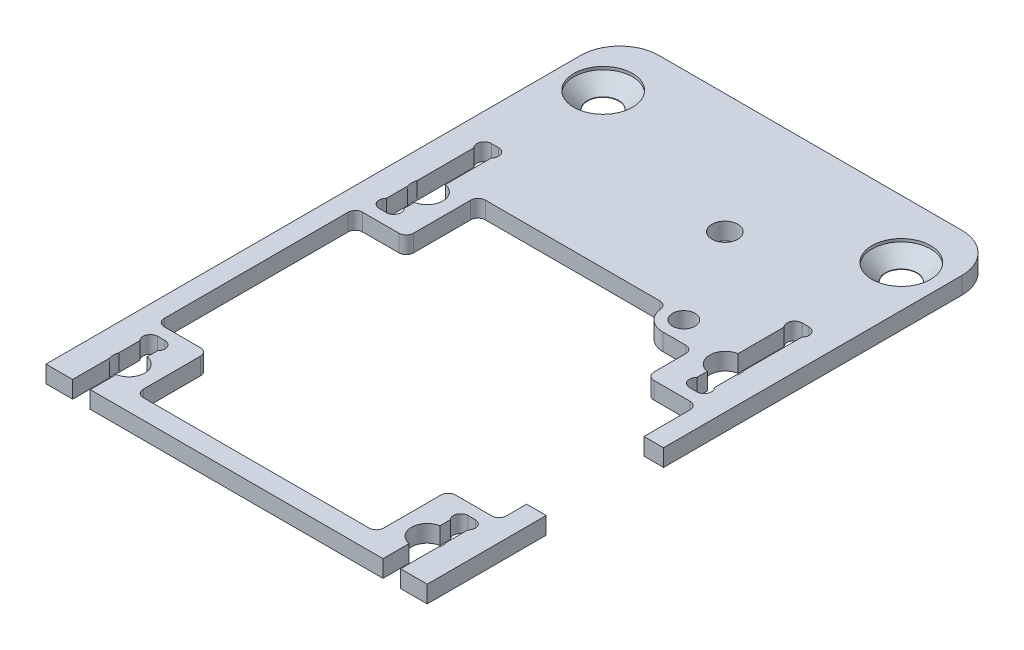
SolidWorks part; units mm, degrees
ref_plane "Front Plane" through (0, 0, 0) normal (0, 0, 1) x (1, 0, 0)
ref_plane "Top Plane" through (0, 0, 0) normal (0, 1, 0) x (1, 0, 0)
ref_plane "Right Plane" through (0, 0, 0) normal (1, 0, 0) x (0, 0, -1)
sketch "Sketch1" plane through (0, 0, 0) normal (0, 1, 0) x (1, 0, 0)
  line L0 (-15.5, 39.2) -> (15.5, 39.2)
  line L1 (-18.2, 15) -> (-18.2, -15) construction
  line L2 (17.5, -17.4996) -> (-17.5, -17.4996)
  line L3 (17.5, -17.4996) -> (17.5, 17.4996)
  line L4 (17.5, 17.4996) -> (-17.5, 17.4996)
  line L5 (-17.5, -17.4996) -> (-17.5, 17.4996)
  line L6 (17.5, -17.4996) -> (-17.5, 17.4996) construction
  line L7 (-19.5, 35.2) -> (-19.5, -19.5)
  line L8 (-19.5, -19.5) -> (19.5, -19.5)
  line L9 (19.5, -19.5) -> (19.5, 35.2)
  line L10 (17.5, 17.4996) -> (-17.5, -17.4996) construction
  line L11 (-15.25, 15.25) -> (-15.25, 17.9996) construction
  line L12 (11.35, 17.05) -> (11.35, 17.4996)
  line L13 (7.05, 17.05) -> (7.05, 17.4996)
  line L14 (15.25, -13.65) -> (15.25, -10.15) construction
  line L15 (17.5, -10.15) -> (12.3, -10.15)
  line L16 (-17.5, -10.15) -> (-12.3, -10.15)
  line L17 (-12.3, -10.15) -> (-12.3, -15.25)
  line L18 (12.3, -10.15) -> (12.3, -15.25)
  line L19 (0, 39.2) -> (0, -19.5) construction
  line L20 (-12.3, -15.25) -> (-12.3, -17.4996)
  line L21 (12.3, -15.25) -> (12.3, -17.4996)
  line L22 (-15.25, 13.65) -> (-15.25, 10.15) construction
  line L23 (-12.3, 17.4996) -> (-17.5, 17.4996)
  line L24 (-12.3, 17.4996) -> (-12.3, 10.15)
  line L25 (-12.3, 10.15) -> (-17.5, 10.15)
  line L26 (-17.5, 17.4996) -> (-17.5, 10.15)
  line L27 (12.3, 17.4996) -> (12.3, 10.15)
  line L28 (12.3, 10.15) -> (17.5, 10.15)
  line L29 (9.2, 14.9) -> (12.3, 14.9)
  arc A0 (19.5, 35.2) -> (15.5, 39.2) centre (15.5, 35.2) ccw construction
  arc A1 (-15.5, 39.2) -> (-19.5, 35.2) centre (-15.5, 35.2) ccw construction
  arc A2 (19.5, 35.2) -> (15.5, 39.2) centre (15.5, 35.2) ccw
  arc A3 (-15.5, 39.2) -> (-19.5, 35.2) centre (-15.5, 35.2) ccw
  circle A4 centre (-15.25, -15.25) radius 1.6 construction
  circle A5 centre (15.25, -15.25) radius 1.6 construction
  circle A6 centre (-15.25, 15.25) radius 1.6 construction
  circle A7 centre (15.25, 15.25) radius 1.6 construction
  circle A8 centre (-15.25, 33.25) radius 1.6 construction
  circle A9 centre (15.25, 33.25) radius 1.6 construction
  circle A10 centre (-15.25, -15.25) radius 1.6
  circle A11 centre (15.25, -15.25) radius 1.6
  circle A12 centre (-15.25, 15.25) radius 1.6
  circle A13 centre (15.25, 15.25) radius 1.6
  circle A14 centre (-15.25, 33.25) radius 1.6
  circle A15 centre (15.25, 33.25) radius 1.6
  arc A16 (-15.2, 18) -> (-18.2, 15) centre (-15.2, 15) ccw construction
  circle A17 centre (-15.25, 15.25) radius 2.95
  circle A18 centre (15.25, 15.25) radius 2.95
  circle A19 centre (-15.25, -15.25) radius 2.95
  circle A20 centre (15.25, -15.25) radius 2.95
  circle A21 centre (3.5, 26.95) radius 1.33 construction
  circle A22 centre (9.2, 17.05) radius 2.15
  circle A23 centre (9.2, 17.05) radius 1.15
  circle A24 centre (9.2, 17.05) radius 0.9 construction
  circle A25 centre (3.5, 26.95) radius 1.33
  point P29 (0, 0)
  dimension "D3" = 2.3
  dimension "D4" = 1
  dimension "D1" = 2
  dimension "D2" = 0.5
  dimension "D6" = 3.5
extrude "Base shape" add sketch "Sketch1" along normal blind 1.75 contours L0 A3 L7 L8 L9 A2 A25 A22 L4 A18 L3 A20 L2 A19 L5 A17 A15 A14 | L23 A17 | A17 L4 L5 | L23 A17 L26 A12 | L26 A17 | A17 L24 L4 | A17 L5 L25 L24 | A23 L4 A22 | A22 L12 L4 | A23 L4 A22 | A22 L29 L27 L4 L12 | A18 L4 L27 | L3 A18 L4 A13 | L4 A18 | A18 L3 L4 | L3 A18 | A18 L27 L28 L3 | A20 L3 L15 L18 | L2 A20 L3 A11 | L3 A20 | A20 L2 L3 | L2 A20 | A20 L21 L2 | L5 A19 | A19 L5 L2 | L2 A19 | L2 A19 L5 A10 | A19 L2 L20 | A19 L17 L16 L5 region at (-0.0675, 0, -21.1692) region at (12.6001, 0, 16.959) region at (-12.6001, 0, 16.959) region at (12.6398, 0, 16.4586) region at (15.25, 0, 17.7828) region at (14.7438, 0, 11.5319) region at (-15.25, 0, 17.7828) region at (-15.25, 0, 17.426) region at (-14.7438, 0, 11.5319) region at (17.3893, 0, 17.3888) region at (17.7831, 0, 15.25) region at (-17.3893, 0, 17.3888) region at (-17.7831, 0, 15.25) region at (14.7438, 0, -11.5319) region at (-14.7438, 0, -11.5319) region at (14.2592, 0, -12.5496) region at (17.7831, 0, -15.25) region at (-17.7831, 0, -15.25) region at (-17.4265, 0, -15.25) region at (17.3893, 0, -17.3888) region at (11.5513, 0, -15.9649) region at (12.6001, 0, -16.959) region at (-17.3893, 0, -17.3888) region at (-12.6001, 0, -16.959) region at (15.25, 0, -17.7828) region at (7.7153, 0, -15.5653) region at (-15.25, 0, -17.7828) region at (11.3358, 0, -17.3874) region at (9.2, 0, -18.3154)
fillet "Milling fillets" radius 0.75 13 edges at (17.5, 0.875, 10.15) (-17.5, 0.875, 10.15) (-12.3, 0.875, 10.15) (12.3, 0.875, 10.15) (12.3, 0.875, 17.4996) (-12.3, 0.875, 17.4996) (17.5, 0.875, -10.15) (12.3, 0.875, -10.15) (12.3, 0.875, -14.9) (7.0975, 0.875, -17.4996) (-12.3, 0.875, -17.4996) (-12.3, 0.875, -10.15) (-17.5, 0.875, -10.15)
sketch "Sketch3" plane through (0, 1.75, 0) normal (0, 1, 0) x (1, 0, 0)
  circle A0 centre (-15.25, 33.25) radius 3
  circle A1 centre (15.25, 33.25) radius 3
  dimension "D1" = 6
extrude "Screw head cut" cut sketch "Sketch3" against normal blind 0.3
chamfer "Screw head chamfer" distance 1.4 angle 45 2 edges at (15.25, 1.45, -31.65) (-15.25, 1.45, -31.65)
sketch "Sketch4" plane through (19.5, 0, 0) normal (1, 0, 0) x (0, 0, -1)
  line L0 (4.175, 1) -> (4.175, 0.2) construction
  line L1 (4.175, 1) -> (4.175, 0.2)
  line L2 (-6.825, 1) -> (-6.825, 0.2) construction
  line L3 (-6.825, 1) -> (-6.825, 0.2)
  line L4 (-6.825, 1) -> (4.175, 0.2) construction
  line L5 (-19.5, 0) -> (35.2, 0) construction
  line L6 (4.675, 0) -> (-7.325, 0)
  line L7 (4.675, 0) -> (4.675, 1.2)
  line L8 (4.675, 1.2) -> (-7.325, 1.2)
  line L9 (-7.325, 0) -> (-7.325, 1.2)
  line L10 (4.675, 0) -> (-7.325, 1.2) construction
  line L11 (4.675, 1.2) -> (-7.325, 0) construction
  line L12 (-19.5, 1.75) -> (35.2, 1.75) construction
  line L13 (4.675, 1.2) -> (-7.325, 1.2)
  line L14 (4.675, 1.2) -> (4.675, 1.75)
  line L15 (4.675, 1.75) -> (-7.325, 1.75)
  line L16 (-7.325, 1.2) -> (-7.325, 1.75)
  point P4 (-1.325, 0.6)
  line M6 (35.2, 1.75) -> (-19.5, 1.75)
  dimension "D1" = 0.5
extrude "SD card cut" cut sketch "Sketch4" against normal up to next contours L9 L7 L8 | L16 L8 L14 M6 region at (19.5, 0.6, 1.325) region at (19.5, 1.475, 1.325)
sketch "Sketch5" plane through (0, 1.75, 0) normal (0, 1, 0) x (1, 0, 0)
  line L0 (-15, 0) -> (15, 0) construction
  line L1 (-15, 0) -> (-16.75, 0) construction
  line L2 (-15.875, -19.5) -> (-15.875, 39.2) construction
  line L3 (-19.5, -19.5) -> (19.5, -19.5) construction
  line L4 (-15.5, 39.2) -> (15.5, 39.2) construction
  line L5 (-15.25, -13.65) -> (-15.25, -11.55) construction
  line L6 (-14.975, -11.55) -> (-16.775, -11.55)
  line L7 (-14.975, -11.55) -> (-14.975, -14.7659)
  line L8 (-14.975, -14.7659) -> (-16.775, -14.7659)
  line L9 (-16.775, -11.55) -> (-16.775, -14.7659)
  line L10 (-14.975, -11.55) -> (-16.775, -14.7659) construction
  line L11 (-14.975, -14.7659) -> (-16.775, -11.55) construction
  line L12 (-16.775, -11.55) -> (-14.975, -13.35) construction
  line L13 (-16.2447, -11.3303) -> (-15.5053, -11.3303)
  line L14 (0, -19.5) -> (0, 39.2) construction
  line L15 (-14.975, -19.5) -> (-16.775, -19.5)
  line L16 (-14.975, -19.5) -> (-14.975, -15.7341)
  line L17 (-14.975, -15.7341) -> (-16.775, -15.7341)
  line L18 (-16.775, -19.5) -> (-16.775, -15.7341)
  line L19 (-14.975, -19.5) -> (-16.775, -15.7341) construction
  line L20 (-14.975, -15.7341) -> (-16.775, -19.5) construction
  line L21 (14.975, -19.5) -> (16.775, -19.5)
  line L22 (14.975, -19.5) -> (14.975, -15.7341)
  line L23 (14.975, -15.7341) -> (16.775, -15.7341)
  line L24 (16.775, -19.5) -> (16.775, -15.7341)
  line L25 (16.775, -11.55) -> (16.775, -14.7659)
  line L26 (14.975, -14.7659) -> (16.775, -14.7659)
  line L27 (14.975, -11.55) -> (14.975, -14.7659)
  line L28 (16.2447, -11.3303) -> (15.5053, -11.3303)
  line L29 (16.775, 11.55) -> (16.775, 14.7659)
  line L30 (16.2447, 11.3303) -> (15.5053, 11.3303)
  line L31 (14.975, 11.55) -> (14.975, 14.7659)
  line L32 (14.975, 14.7659) -> (16.775, 14.7659)
  line L33 (-16.775, 11.55) -> (-16.775, 14.7659)
  line L34 (-16.2447, 11.3303) -> (-15.5053, 11.3303)
  line L35 (-14.975, 11.55) -> (-14.975, 14.7659)
  line L36 (-14.975, 14.7659) -> (-16.775, 14.7659)
  line L37 (-15.25, 16.85) -> (-15.25, 22.6) construction
  line L38 (-16.775, 22.6) -> (-14.975, 22.6)
  line L39 (-16.775, 22.6) -> (-16.775, 15.7341)
  line L40 (-16.775, 15.7341) -> (-14.975, 15.7341)
  line L41 (-14.975, 22.6) -> (-14.975, 15.7341)
  line L42 (-16.775, 22.6) -> (-14.975, 15.7341) construction
  line L43 (-16.775, 15.7341) -> (-14.975, 22.6) construction
  line L44 (-16.775, 22.6) -> (-14.975, 20.8) construction
  line L45 (-16.2447, 22.8197) -> (-15.5053, 22.8197)
  line L46 (16.2447, 22.8197) -> (15.5053, 22.8197)
  line L47 (14.975, 22.6) -> (14.975, 15.7341)
  line L48 (16.775, 15.7341) -> (14.975, 15.7341)
  line L49 (16.775, 22.6) -> (16.775, 15.7341)
  circle A0 centre (-15.25, -15.25) radius 1.6 construction
  circle A1 centre (-16.2447, -12.0803) radius 0.75
  circle A2 centre (-15.5053, -12.0803) radius 0.75
  circle A3 centre (15.5053, -12.0803) radius 0.75
  circle A4 centre (16.2447, -12.0803) radius 0.75
  circle A5 centre (16.2447, 12.0803) radius 0.75
  circle A6 centre (15.5053, 12.0803) radius 0.75
  circle A7 centre (-16.2447, 12.0803) radius 0.75
  circle A8 centre (-15.5053, 12.0803) radius 0.75
  circle A9 centre (-15.25, 15.25) radius 1.6 construction
  circle A10 centre (-16.2447, 22.0697) radius 0.75
  circle A11 centre (-15.5053, 22.0697) radius 0.75
  circle A12 centre (16.2447, 22.0697) radius 0.75
  circle A13 centre (15.5053, 22.0697) radius 0.75
  point P3 (0, 0)
  point P11 (-15.875, 0)
  point P12 (-15.875, -13.1579)
  point P29 (-15.875, -17.6171)
  point P70 (-15.875, 19.1671)
  circle M12 centre (-15.25, 15.25) radius 1.6
  circle M13 centre (-15.25, -15.25) radius 1.6
  circle M14 centre (15.25, -15.25) radius 1.6
  circle M15 centre (15.25, 15.25) radius 1.6
  line M52 (-19.5, -19.5) -> (19.5, -19.5)
  dimension "D6" = 1.5
  dimension "D9" = 1.5
  dimension "D1" = 30
  dimension "D2" = 1.75
  dimension "D3" = 1.8
  dimension "D4" = 2.1
  dimension "D5" = 45
  dimension "D7" = 5.75
  dimension "D8" = 45
extrude "Tab cuts" cut sketch "Sketch5" against normal up to next contours L7 A2 A1 L9 M13 | L9 A1 | A1 A2 L6 L9 | L6 A2 A1 | A2 A1 L6 | A2 L6 A1 | A1 A2 L13 | A2 A1 L6 | A2 L7 L6 A1 | A2 L7 | L18 L16 M52 M13 | L27 A3 | A3 A4 L27 | A3 A4 L28 | A4 A3 L25 | A4 A3 | A4 L25 | L25 A4 A3 L27 M14 | L24 L22 M52 M14 | A8 L35 L33 A7 M12 | A7 L33 | A8 A7 L33 | A7 A8 | L35 A8 A7 | L35 A8 | A8 A7 L34 | L31 A6 A5 L29 M15 | A6 L31 | A6 L31 A5 | A5 A6 L30 | A6 A5 | A5 A6 L29 | L29 A5 | A10 A11 L45 | L38 A11 A10 | A11 L38 A10 | A11 A10 L38 | A11 L41 | A11 L41 L38 A10 | A11 A10 L38 | A10 A11 L38 L39 | L39 A10 | L41 A11 A10 L39 M12 | L47 A13 | A12 A13 L47 | A13 A12 L46 | A12 A13 | A13 A12 L49 | A12 L49 | A13 L47 L49 A12 M15 region at (-15.3045, 1.75, 12.1946) region at (-14.8859, 1.75, 12.0803) region at (15.9224, 1.75, 18.0336) region at (-15.4482, 1.75, 11.4538) region at (-15.875, 1.75, 12.0983) region at (-15.875, 1.75, 11.5073) region at (-15.9972, 1.75, 13.3769) region at (-15.875, 1.75, 11.3592) region at (-16.4455, 1.75, 12.1946) region at (-16.3018, 1.75, 11.4538) region at (-16.8641, 1.75, 12.0803) region at (-15.9224, 1.75, 18.0336) region at (15.9972, 1.75, 13.3769) region at (14.8859, 1.75, 12.0803) region at (15.3267, 1.75, 12.0803) region at (15.875, 1.75, 12.0803) region at (16.4233, 1.75, 12.0803) region at (16.8641, 1.75, 12.0803) region at (15.875, 1.75, 11.3592) region at (16.4233, 1.75, -12.0803) region at (16.8641, 1.75, -12.0803) region at (15.9972, 1.75, -13.3769) region at (15.875, 1.75, -11.3592) region at (15.875, 1.75, -12.0803) region at (15.3267, 1.75, -12.0803) region at (14.8859, 1.75, -12.0803) region at (15.9038, 1.75, -18.9762) region at (16.4233, 1.75, -22.0697) region at (16.8641, 1.75, -22.0697) region at (14.8859, 1.75, -22.0697) region at (15.3267, 1.75, -22.0697) region at (15.875, 1.75, -22.0697) region at (15.875, 1.75, -22.7908) region at (-16.8641, 1.75, -12.0803) region at (-16.4233, 1.75, -12.0803) region at (-15.9972, 1.75, -13.3769) region at (-15.875, 1.75, -11.3592) region at (-15.3267, 1.75, -12.0803) region at (-15.875, 1.75, -12.0803) region at (-15.9038, 1.75, -18.9762) region at (-14.8859, 1.75, -12.0803) region at (-16.8641, 1.75, -22.0697) region at (-16.4455, 1.75, -21.9554) region at (-16.3018, 1.75, -22.6962) region at (-15.875, 1.75, -22.0517) region at (-15.3045, 1.75, -21.9554) region at (-14.8859, 1.75, -22.0697) region at (-15.875, 1.75, -22.6427) region at (-15.875, 1.75, -22.7908) region at (-15.4482, 1.75, -22.6962)
